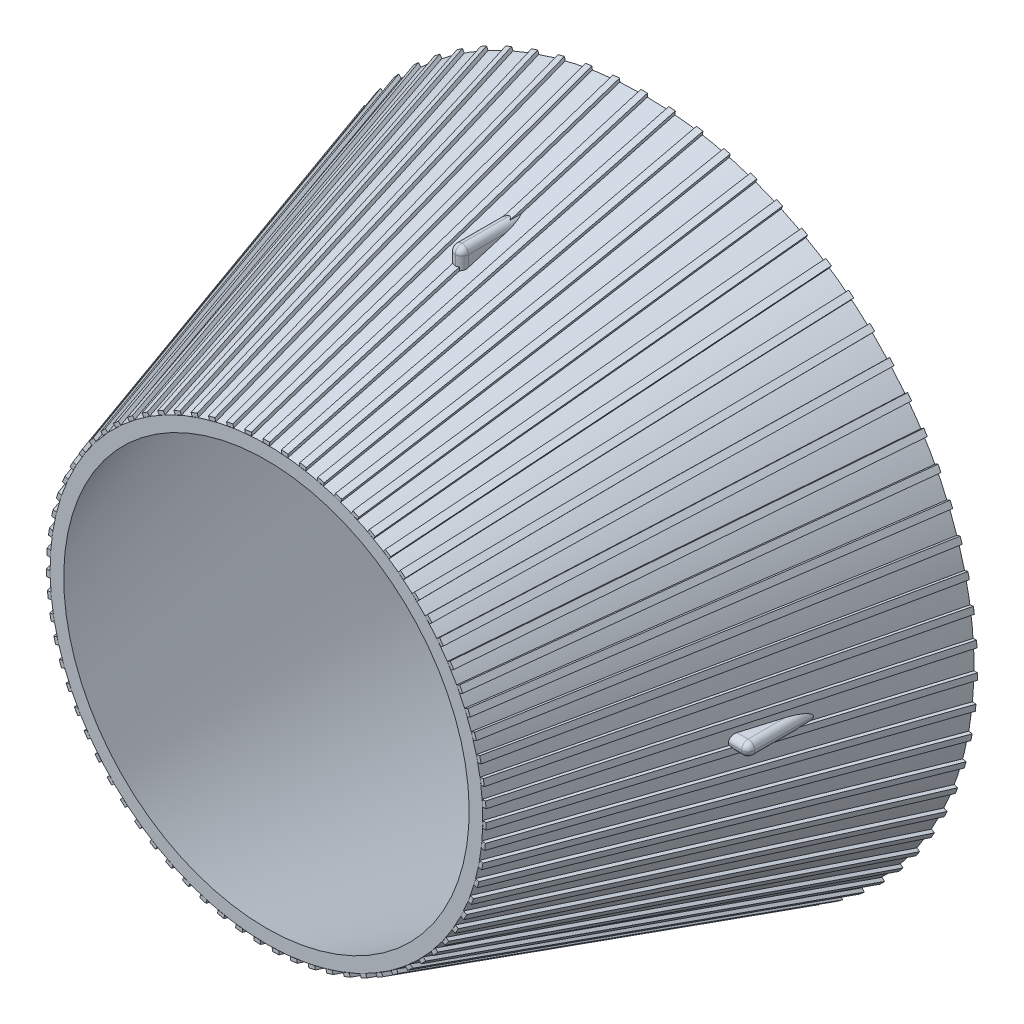
SolidWorks part; units mm, degrees
note: '?' marks a value the reader was unsure of.
ref_plane "Piano frontale" through (0, 0, 0) normal (0, 0, 1) x (1, 0, 0)
ref_plane "Piano superiore" through (0, 0, 0) normal (0, 1, 0) x (1, 0, 0)
ref_plane "Piano destro" through (0, 0, 0) normal (1, 0, 0) x (0, 0, -1)
sketch "Schizzo5" plane through (0, 0, 0) normal (1, 0, 0) x (0, 0, -1)
  line L6 (-5760, 0) -> (0, 0)
  line L7 (0, 4821.1739) -> (-5760, 3091.1739)
  line L8 (-5760, 3300) -> (-5760, 3091.1739)
  line L9 (0, 5030) -> (-5760, 3300)
  line L10 (0, 4821.1739) -> (0, 5030)
revolve "Rivoluzione3" add sketch "Schizzo5" angle 360 about L6
ref_axis "Assi2" through (0, 0, 0) along (0, 0, 1)?
sketch "Schizzo6" plane through (0, 0, 0) normal (1, 0, 0) x (0, 0, -1)
  line L0 (0, 5030) -> (-5760, 3300) construction
  line L1 (0, 5030) -> (-5760, 3300)
  line L2 (0, 5030) -> (0, 5082.2065)
  line L3 (0, 5082.2065) -> (-5760.6079, 3352.0239)
  line L4 (-5760.6079, 3352.0239) -> (-5760, 3300)
  dimension "D1" = 50
extrude "Estrusione-Estrusione1" add sketch "Schizzo6" along normal mid plane 100 separate body
pattern_circular "RipetizioneCircolare1" count 75 over 360 about axis through (0, 0, 0) along (0, 0, 1)
sketch "Schizzo7" plane through (0, 0, 0) normal (1, 0, 0) x (0, 0, -1)
  line L0 (-5760, 3300) -> (-5760, -3300) construction
  line L1 (-5760, 3300) -> (-5760, -3300)
  line L2 (0, -5030) -> (0, 5030) construction
  line L3 (0, -5030) -> (0, 5030)
  line L4 (-5760, 3300) -> (0, 5030)
  line L5 (-2880, 4465) -> (-2880, -38.3295)
  line L6 (0, -56.4447) -> (-5760.6079, -20.2105) construction
  line L7 (-2880, 4465) -> (-1881.1561, 4465)
  line L8 (-2880, -38.3295) -> (-2880, -4465)
  line L9 (-5760, -3300) -> (0, -5030)
  line L10 (-2880, -4465) -> (-1881.1561, -4465)
  point P8 (-2880, 4165)
  point P9 (-2880, -4165)
  dimension "D1" = 2880
  dimension "D2" = 300
  dimension "D3" = 300
extrude "Estrusione-Estrusione2" add sketch "Schizzo7" along normal mid plane 200 contours L7 L5 L4 | L8 L10 L9
fillet "Raccordo1" radius 100 4 edges at (100, 4465, 2380.578) (100, 4315, 2880) (-100, 4315, 2880) (-100, 4465, 2380.578)
fillet "Raccordo2" radius 100 4 edges at (100, -4465, 2380.578) (-100, -4465, 2380.578) (-100, -4315, 2880) (100, -4315, 2880)
sketch "Schizzo9" plane through (0, 0, 0) normal (0, 1, 0) x (1, 0, 0)
  line L0 (5030, 0) -> (-5030, 0) construction
  line L1 (5030, 0) -> (-5030, 0)
  line L2 (-3300, -5760) -> (3300, -5760) construction
  line L3 (-3300, -5760) -> (3300, -5760)
  line L4 (-5030, 0) -> (-3300, -5760)
  line L5 (3300, -5760) -> (5030, 0)
  line L6 (-4465, -2880) -> (4465, -2880)
  line L7 (-4465, -2880) -> (-4465, -1881.1561)
  line L9 (4465, -2880) -> (4465, -1881.1561)
  point P6 (-4165, -2880)
  point P7 (4165, -2880)
  dimension "D1" = 2880
  dimension "D2" = 300
  dimension "D3" = 300
extrude "Estrusione-Estrusione3" add sketch "Schizzo9" along normal mid plane 200 contours L7 L6 L4 | L6 L9 L5
fillet "Raccordo3" radius 100 4 edges at (4340.5185, -100, 2880) (4465, -100, 2465.6321) (4465, 100, 2380.578) (4315, 100, 2880)
fillet "Raccordo4" radius 100 4 edges at (-4340.5185, -100, 2880) (-4315, 100, 2880) (-4465, 100, 2380.578) (-4465, -100, 2465.6321)
